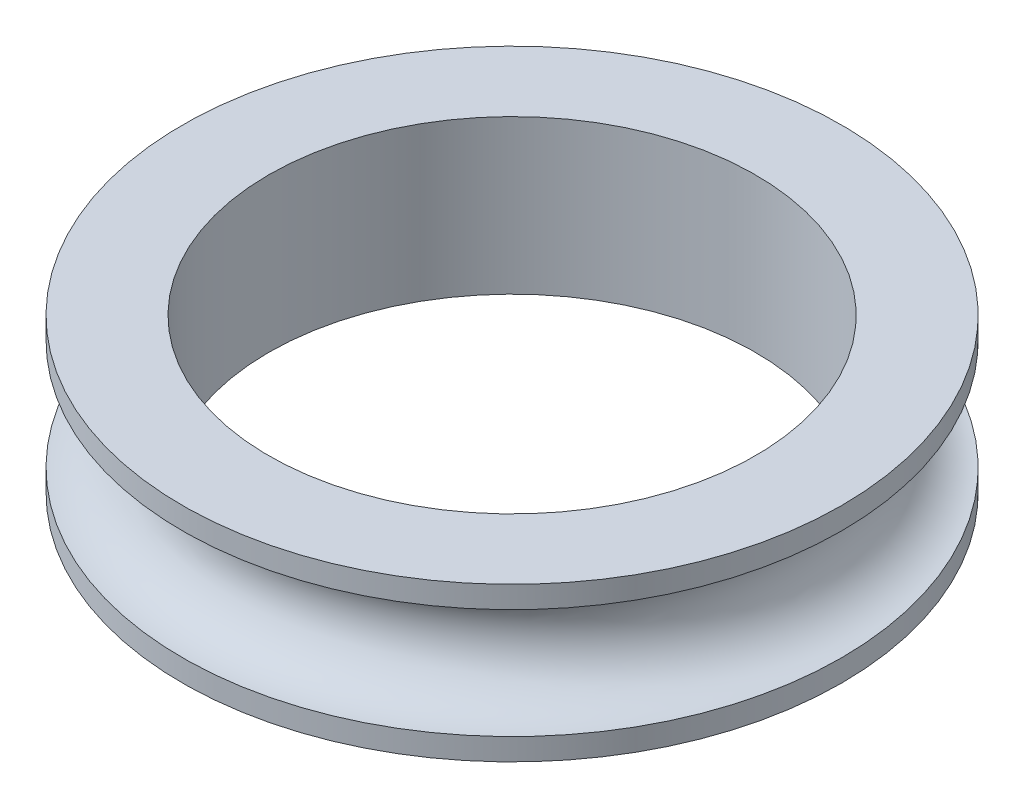
SolidWorks part; units mm, degrees
ref_plane "Front Plane" through (0, 0, 0) normal (0, 0, 1) x (1, 0, 0)
ref_plane "Top Plane" through (0, 0, 0) normal (0, 1, 0) x (1, 0, 0)
ref_plane "Right Plane" through (0, 0, 0) normal (1, 0, 0) x (0, 0, -1)
sketch "Sketch2" plane through (0, 0, 0) normal (0, 0, 1) x (1, 0, 0)
  line L0 (-15, 2.5) -> (-15, 3.5)
  line L5 (0, -3.5) -> (-15, -3.5)
  line L6 (0, -3.5) -> (0, 3.5)
  line L7 (0, 3.5) -> (-15, 3.5)
  line L8 (-15, -3.5) -> (-15, -2.5)
  arc A0 (-15, -2.5) -> (-15, 2.5) centre (-15, 0) ccw
  point P5 (0, 0)
  point P8 (0, 0)
  point P11 (0, 4.9805)
  point P12 (0, 0)
  point P14 (-7.8328, 4.5)
  dimension "D2" = 2.5
  dimension "D3" = 1
  dimension "D1" = 7
  dimension "D5" = 15
ref_axis "Axis1" through (0, -3.5, 0) along (0, 1, 0)
revolve "Revolve1" add sketch "Sketch2" angle 360 about L6
sketch "Sketch4" plane through (0, 3.5, 0) normal (0, 1, 0) x (1, 0, 0)
  circle A0 centre (0, 0) radius 11.075
  dimension "D1" = 22.15
extrude "Cut-Extrude1" cut sketch "Sketch4" against normal through all contours A0
